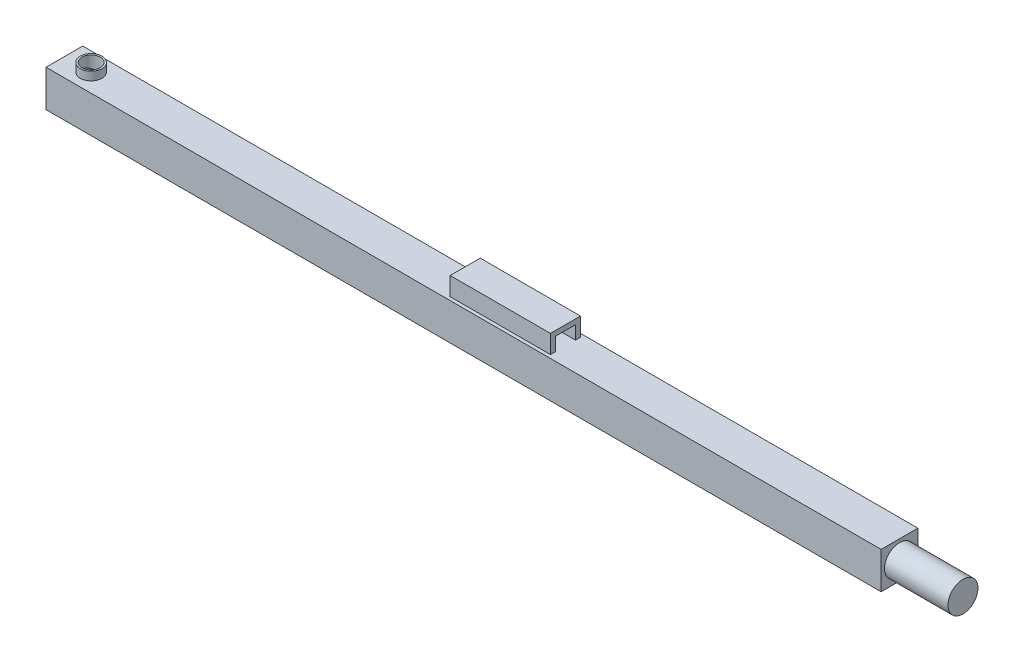
SolidWorks part; units mm, degrees
ref_plane "Front Plane" through (0, 0, 0) normal (0, 0, 1) x (1, 0, 0)
ref_plane "Top Plane" through (0, 0, 0) normal (0, 1, 0) x (1, 0, 0)
ref_plane "Right Plane" through (0, 0, 0) normal (1, 0, 0) x (0, 0, -1)
sketch "Sketch1" plane through (0, 0, 0) normal (1, 0, 0) x (0, 0, -1)
  circle A0 centre (0, 0) radius 4.5
  dimension "D1" = 9
extrude "Boss-Extrude1" add sketch "Sketch1" along normal blind 19
sketch "Sketch2" plane through (0, 0, 0) normal (1, 0, 0) x (0, 0, -1)
  line L1 (-5.5, 5.5) -> (5.5, 5.5)
  line L2 (-5.5, 5.5) -> (-5.5, -5.5)
  line L3 (-5.5, -5.5) -> (5.5, -5.5)
  line L4 (5.5, 5.5) -> (5.5, -5.5)
  line L5 (-5.5, 5.5) -> (5.5, -5.5) construction
  line L6 (-5.5, -5.5) -> (5.5, 5.5) construction
  point P0 (0, 0)
  dimension "D1" = 11
extrude "Boss-Extrude2" add sketch "Sketch2" against normal blind 250
sketch "Sketch3" plane through (-250, 0, 0) normal (-1, 0, 0) x (0, 0, 1)
  circle A0 centre (0, 0) radius 4.85
  dimension "D1" = 9.7
extrude "Cut-Extrude2" cut sketch "Sketch3" against normal blind 19.5
sketch "Sketch4" plane through (0, 0, 0) normal (1, 0, 0) x (0, 0, -1)
  line L0 (5.5, 5.5) -> (-5.5, 5.5) construction
  line L1 (-4.5, 11) -> (4.5, 11)
  line L2 (-4.5, 11) -> (-4.5, 5.5)
  line L3 (-4.5, 5.5) -> (-3, 5.5)
  line L4 (4.5, 11) -> (4.5, 5.5)
  line L5 (4.5, 11) -> (-4.5, 5.5) construction
  line L6 (-3, 9.5) -> (3, 9.5)
  line L7 (-3, 9.5) -> (-3, 5.5)
  line L9 (3, 9.5) -> (3, 5.5)
  line L10 (3, 9.5) -> (-3, 5.5) construction
  line L11 (3, 5.5) -> (4.5, 5.5)
  line L13 (5.5, -5.5) -> (5.5, 5.5) construction
  point P10 (0, 7.5)
  point P11 (0, 8.25)
  dimension "D1" = 1.5
  dimension "D2" = 1.5
  dimension "D3" = 4
  dimension "D4" = 1
extrude "Boss-Extrude3" add sketch "Sketch4" against normal blind 30 from offset 100 offset against normal yes
sketch "Sketch5" plane through (0, 5.5, 0) normal (0, 1, 0) x (1, 0, 0)
  line L0 (-9.075, 0) -> (9.075, 0) construction
  line L1 (-250, 5.5) -> (-250, -5.5) construction
  circle A0 centre (-242, 0) radius 2.75
  circle A1 centre (-242, 0) radius 3.25
  dimension "D1" = 5.5
  dimension "D2" = 6.5
  dimension "D3" = 8
extrude "Cut-Extrude3" cut sketch "Sketch5" against normal up to surface (1.505 mm away) contours A0 up to face at (-230.5, 0, 4.85)
extrude "Boss-Extrude4" add sketch "Sketch5<3>" along normal blind 2.5 contours A1 A0 region at (-245.1581, 5.5, 0)
sketch "Sketch5<3>" plane through (0, 5.5, 0) normal (0, 1, 0) x (1, 0, 0) same geometry as "Sketch5"
